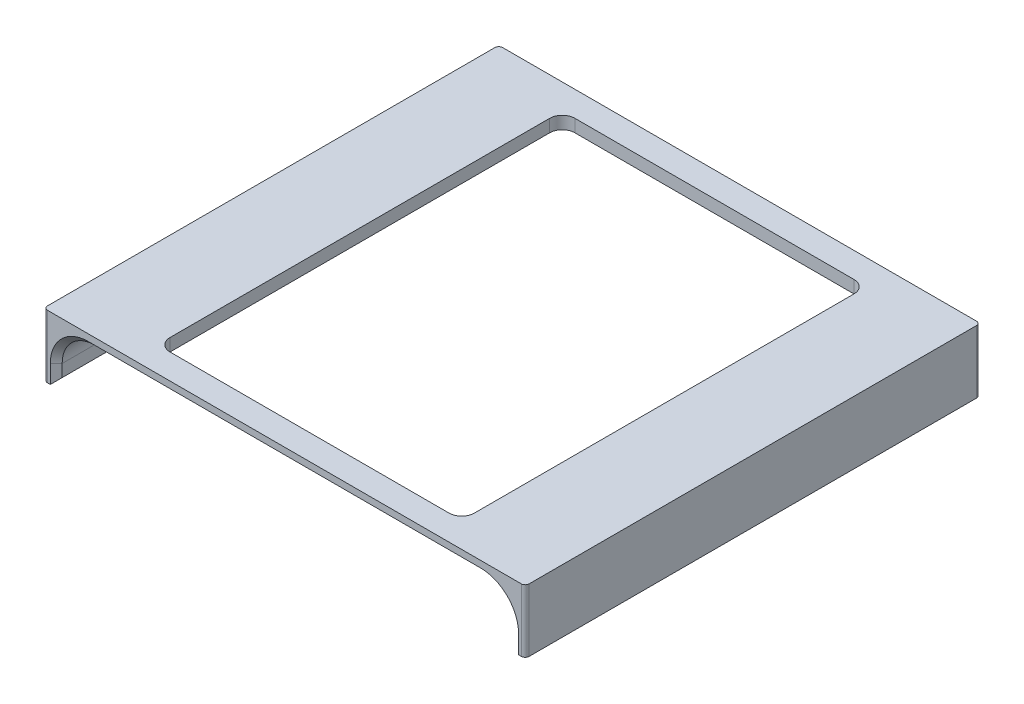
SolidWorks part; units mm, degrees
ref_plane "Front Plane" through (0, 0, 0) normal (0, 0, 1) x (1, 0, 0)
ref_plane "Top Plane" through (0, 0, 0) normal (0, 1, 0) x (1, 0, 0)
ref_plane "Right Plane" through (0, 0, 0) normal (1, 0, 0) x (0, 0, -1)
sketch "Sketch1" plane through (0, 0, 0) normal (0, 1, 0) x (1, 0, 0)
  line L0 (0, 57.4675) -> (0, -57.4675) construction
  line L1 (-35.2425, 51.1175) -> (35.2425, 51.1175)
  line L2 (-38.4175, 47.9425) -> (-38.4175, -47.9425)
  line L3 (-35.2425, -51.1175) -> (35.2425, -51.1175)
  line L4 (38.4175, 47.9425) -> (38.4175, -47.9425)
  line L5 (-38.4175, 0) -> (38.4175, 0) construction
  line L7 (-57.6326, 57.4675) -> (57.6326, 57.4675)
  line L8 (-57.6326, 57.4675) -> (-57.6326, -57.4675)
  line L9 (-57.6326, -57.4675) -> (57.6326, -57.4675)
  line L10 (57.6326, 57.4675) -> (57.6326, -57.4675)
  line L11 (-57.6326, 57.4675) -> (-60.8076, 57.4675)
  line L12 (-57.6326, 57.4675) -> (-57.6326, -57.4675)
  line L13 (-57.6326, -57.4675) -> (-60.8076, -57.4675)
  line L14 (-60.8076, 57.4675) -> (-60.8076, -57.4675)
  line L15 (57.6326, 57.4675) -> (60.8076, 57.4675)
  line L16 (57.6326, 57.4675) -> (57.6326, -57.4675)
  line L17 (57.6326, -57.4675) -> (60.8076, -57.4675)
  line L18 (60.8076, 57.4675) -> (60.8076, -57.4675)
  arc A0 (35.2425, 51.1175) -> (38.4175, 47.9425) centre (35.2425, 47.9425) cw
  arc A1 (35.2425, -51.1175) -> (38.4175, -47.9425) centre (35.2425, -47.9425) ccw
  arc A2 (-38.4175, -47.9425) -> (-35.2425, -51.1175) centre (-35.2425, -47.9425) ccw
  arc A3 (-35.2425, 51.1175) -> (-38.4175, 47.9425) centre (-35.2425, 47.9425) ccw
  point P11 (0, 0)
  point P14 (0, 0)
  point P18 (38.4175, 51.1175)
  point P23 (-38.4175, -51.1175)
  point P26 (-38.4175, 51.1175)
  point P33 (-57.3151, -64.9521)
  dimension "D5" = 3.175
  dimension "D1" = 76.835
  dimension "D2" = 102.235
  dimension "D3" = 115.2652
  dimension "D4" = 6.35
  dimension "D6" = 3.175
extrude "Boss-Extrude1" add sketch "Sketch1" along normal blind 3.175 contours L10 L7 L8 L9 A3 L1 A0 L4 A1 L3 A2 L2 | L11 L14 L13 L8 | L15 L18 L17 L16 region at (0, 0, -55.8397) region at (-59.2201, 0, 0)
extrude "Boss-Extrude2" add sketch "Sketch1<3>" against normal blind 12.7 contours L18 L15 L10 L17 | L11 L14 L13 L8 region at (-59.2201, 0, 0) region at (59.2201, 0, 0)
sketch "Sketch1<3>" plane through (0, 0, 0) normal (0, 1, 0) x (1, 0, 0) same geometry as "Sketch1"
fillet "Fillet1" radius 8.1001 2 edges at (57.6326, 0, 0) (-57.6326, 0, 0)
chamfer "Chamfer1" distance 1.5 angle 45 12 edges at (-57.6326, -10.4, 57.4675) (-55.2601, -2.3725, 57.4675) (0, 0, 57.4675) (55.2601, -2.3725, 57.4675) (57.6326, -12.7, 0) (57.6326, -10.4, 57.4675) (57.6326, -10.4, -57.4675) (55.2601, -2.3725, -57.4675) (0, 0, -57.4675) (-55.2601, -2.3725, -57.4675) (-57.6326, -12.7, 0) (-57.6326, -10.4, -57.4675)
fillet "Fillet2" radius 1 4 edges at (-60.8076, -4.7625, 57.4675) (-60.8076, -4.7625, -57.4675) (60.8076, -4.7625, -57.4675) (60.8076, -4.7625, 57.4675)
